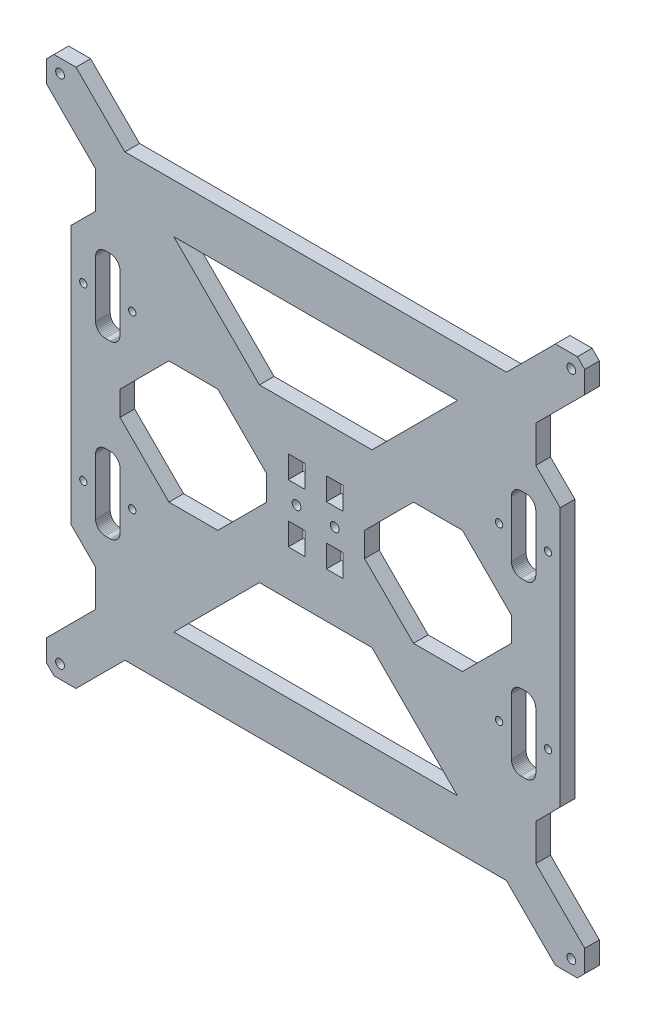
SolidWorks part; units mm, degrees
ref_plane "Plano frontal" through (0, 0, 0) normal (0, 0, 1) x (1, 0, 0)
ref_plane "Plano superior" through (0, 0, 0) normal (0, 1, 0) x (1, 0, 0)
ref_plane "Plano direito" through (0, 0, 0) normal (1, 0, 0) x (0, 0, -1)
sketch "Model" plane through (0, 0, 0) normal (0, 0, 1) x (1, 0, 0)
  line L0 (50.4714, 105.5211) -> (50.0021, 105.2896)
  line L1 (49.567, 104.999) -> (49.1737, 104.654)
  line L2 (50.0021, 105.2896) -> (49.567, 104.999)
  line L3 (40.0021, 14.8256) -> (60.0021, 34.8256)
  line L4 (38.0021, 71.8256) -> (48.0021, 61.8256)
  line L5 (48.0021, 187.8255) -> (38.0021, 177.8255)
  line L6 (28.0021, 26.8256) -> (28.0021, 17.8256)
  line L7 (56.8305, 75.9971) -> (57.1755, 76.3905)
  line L8 (55.5328, 105.5211) -> (55.0374, 105.6892)
  line L9 (55.0374, 105.6892) -> (54.5242, 105.7913)
  line L10 (54.5242, 105.7913) -> (54.0021, 105.8255)
  line L11 (28.0021, 17.8256) -> (31.0021, 14.8256)
  line L12 (57.9679, 78.3034) -> (58.0021, 78.8256)
  line L13 (54.5242, 74.8598) -> (55.0374, 74.9619)
  line L14 (50.4714, 75.13) -> (50.9668, 74.9619)
  line L15 (50.0021, 75.3615) -> (50.4714, 75.13)
  line L16 (56.0021, 105.2896) -> (55.5328, 105.5211)
  line L17 (48.3066, 103.3563) -> (48.1384, 102.8608)
  line L18 (48.1384, 102.8608) -> (48.0363, 102.3476)
  line L19 (48.0363, 102.3476) -> (48.0021, 101.8255)
  line L20 (52.0021, 105.8255) -> (54.0021, 105.8255)
  line L21 (40.0021, 234.8255) -> (60.0021, 214.8255)
  line L22 (49.567, 75.6521) -> (50.0021, 75.3615)
  line L23 (49.1737, 75.9971) -> (49.567, 75.6521)
  line L24 (54.0021, 74.8256) -> (52.0021, 74.8256)
  line L25 (52.0021, 105.8255) -> (51.48, 105.7913)
  line L26 (51.48, 105.7913) -> (50.9668, 105.6892)
  line L27 (48.0021, 78.8256) -> (48.0021, 101.8255)
  line L28 (48.0021, 78.8256) -> (48.0363, 78.3034)
  line L29 (48.0363, 78.3034) -> (48.1384, 77.7903)
  line L30 (28.0021, 222.8255) -> (48.0021, 202.8255)
  line L31 (57.8658, 102.8608) -> (57.6976, 103.3563)
  line L32 (57.9679, 102.3476) -> (57.8658, 102.8608)
  line L33 (58.0021, 101.8255) -> (57.9679, 102.3476)
  line L34 (31.0021, 234.8255) -> (28.0021, 231.8255)
  line L35 (38.0021, 177.8255) -> (38.0021, 71.8256)
  line L36 (57.6976, 103.3563) -> (57.4662, 103.8255)
  line L37 (57.4662, 103.8255) -> (57.1755, 104.2606)
  line L38 (48.0021, 46.8256) -> (48.0021, 61.8256)
  line L39 (48.3066, 77.2948) -> (48.538, 76.8256)
  line L40 (48.538, 76.8256) -> (48.8287, 76.3905)
  line L41 (57.1755, 104.2606) -> (56.8305, 104.654)
  line L42 (48.8287, 76.3905) -> (49.1737, 75.9971)
  line L43 (58.0021, 101.8255) -> (58.0021, 78.8256)
  line L44 (48.538, 103.8255) -> (48.3066, 103.3563)
  line L45 (55.5328, 75.13) -> (56.0021, 75.3615)
  line L46 (56.0021, 75.3615) -> (56.4371, 75.6521)
  line L47 (56.4371, 75.6521) -> (56.8305, 75.9971)
  line L48 (55.0374, 74.9619) -> (55.5328, 75.13)
  line L49 (57.6976, 77.2948) -> (57.8658, 77.7903)
  line L50 (57.8658, 77.7903) -> (57.9679, 78.3034)
  line L51 (56.4371, 104.999) -> (56.0021, 105.2896)
  line L52 (56.8305, 104.654) -> (56.4371, 104.999)
  line L53 (28.0021, 26.8256) -> (48.0021, 46.8256)
  line L54 (48.0021, 202.8255) -> (48.0021, 187.8255)
  line L55 (50.9668, 105.6892) -> (50.4714, 105.5211)
  line L56 (54.0021, 74.8256) -> (54.5242, 74.8598)
  line L57 (50.9668, 74.9619) -> (51.48, 74.8598)
  line L58 (48.8287, 104.2606) -> (48.538, 103.8255)
  line L59 (49.1737, 104.654) -> (48.8287, 104.2606)
  line L60 (57.1755, 76.3905) -> (57.4662, 76.8256)
  line L61 (57.4662, 76.8256) -> (57.6976, 77.2948)
  line L62 (48.1384, 77.7903) -> (48.3066, 77.2948)
  line L63 (51.48, 74.8598) -> (52.0021, 74.8256)
  line L64 (60.0021, 214.8255) -> (216.002, 214.8255)
  line L65 (60.0021, 34.8256) -> (216.002, 34.8256)
  line L66 (57.8658, 172.8678) -> (57.6976, 173.3633)
  line L67 (57.6976, 173.3633) -> (57.4662, 173.8326)
  line L68 (57.1755, 174.2676) -> (56.8305, 174.661)
  line L69 (57.9679, 172.3547) -> (57.8658, 172.8678)
  line L70 (58.0021, 171.8326) -> (57.9679, 172.3547)
  line L71 (58.0021, 171.8326) -> (58.0021, 148.8326)
  line L72 (57.9679, 148.3105) -> (58.0021, 148.8326)
  line L73 (57.8658, 147.7973) -> (57.9679, 148.3105)
  line L74 (57.6976, 147.3018) -> (57.8658, 147.7973)
  line L75 (57.4662, 146.8326) -> (57.6976, 147.3018)
  line L76 (57.1755, 146.3975) -> (57.4662, 146.8326)
  line L77 (56.8305, 146.0041) -> (57.1755, 146.3975)
  line L78 (56.4371, 145.6592) -> (56.8305, 146.0041)
  line L79 (56.0021, 145.3685) -> (56.4371, 145.6592)
  line L80 (55.5328, 145.1371) -> (56.0021, 145.3685)
  line L81 (55.0374, 144.9689) -> (55.5328, 145.1371)
  line L82 (54.5242, 144.8668) -> (55.0374, 144.9689)
  line L83 (54.0021, 144.8326) -> (54.5242, 144.8668)
  line L84 (54.0021, 144.8326) -> (52.0021, 144.8326)
  line L85 (51.48, 144.8668) -> (52.0021, 144.8326)
  line L86 (50.9668, 144.9689) -> (51.48, 144.8668)
  line L87 (50.4714, 145.1371) -> (50.9668, 144.9689)
  line L88 (50.0021, 145.3685) -> (50.4714, 145.1371)
  line L89 (49.567, 145.6592) -> (50.0021, 145.3685)
  line L90 (49.1737, 146.0041) -> (49.567, 145.6592)
  line L91 (48.8287, 146.3975) -> (49.1737, 146.0041)
  line L92 (48.538, 146.8326) -> (48.8287, 146.3975)
  line L93 (48.3066, 147.3018) -> (48.538, 146.8326)
  line L94 (48.1384, 147.7973) -> (48.3066, 147.3018)
  line L95 (48.0363, 148.3105) -> (48.1384, 147.7973)
  line L96 (48.0021, 148.8326) -> (48.0363, 148.3105)
  line L97 (48.0021, 148.8326) -> (48.0021, 171.8326)
  line L98 (48.0363, 172.3547) -> (48.0021, 171.8326)
  line L99 (48.1384, 172.8678) -> (48.0363, 172.3547)
  line L100 (48.3066, 173.3633) -> (48.1384, 172.8678)
  line L101 (48.538, 173.8326) -> (48.3066, 173.3633)
  line L102 (48.8287, 174.2676) -> (48.538, 173.8326)
  line L103 (49.1737, 174.661) -> (48.8287, 174.2676)
  line L104 (49.567, 175.006) -> (49.1737, 174.661)
  line L105 (50.0021, 175.2967) -> (49.567, 175.006)
  line L106 (50.4714, 175.5281) -> (50.0021, 175.2967)
  line L107 (50.9668, 175.6963) -> (50.4714, 175.5281)
  line L108 (51.48, 175.7983) -> (50.9668, 175.6963)
  line L109 (52.0021, 175.8326) -> (51.48, 175.7983)
  line L110 (52.0021, 175.8326) -> (54.0021, 175.8326)
  line L111 (54.5242, 175.7983) -> (54.0021, 175.8326)
  line L112 (55.0374, 175.6963) -> (54.5242, 175.7983)
  line L113 (55.5328, 175.5281) -> (55.0374, 175.6963)
  line L114 (56.0021, 175.2967) -> (55.5328, 175.5281)
  line L115 (56.4371, 175.006) -> (56.0021, 175.2967)
  line L116 (56.8305, 174.661) -> (56.4371, 175.006)
  line L117 (57.4662, 173.8326) -> (57.1755, 174.2676)
  line L118 (80.0021, 194.8255) -> (115.0021, 159.8255)
  line L119 (118.0021, 129.8255) -> (118.0021, 119.8255)
  line L120 (118.0021, 119.8255) -> (98.0021, 99.8255)
  line L121 (98.0021, 99.8255) -> (78.0021, 99.8255)
  line L122 (78.0021, 99.8255) -> (58.0021, 119.8255)
  line L123 (58.0021, 119.8255) -> (58.0021, 129.8255)
  line L124 (58.0021, 129.8255) -> (78.0021, 149.8255)
  line L125 (78.0021, 149.8255) -> (98.0021, 149.8255)
  line L126 (98.0021, 149.8255) -> (118.0021, 129.8255)
  line L127 (115.0021, 89.8255) -> (80.0021, 54.8256)
  line L128 (126.8002, 117.5591) -> (126.8002, 108.3591)
  line L129 (126.8002, 141.3591) -> (126.8002, 132.1591)
  line L130 (133.6002, 108.3591) -> (133.6002, 117.5591)
  line L131 (133.6002, 117.5591) -> (126.8002, 117.5591)
  line L132 (133.6002, 141.3591) -> (126.8002, 141.3591)
  line L133 (126.8002, 132.1591) -> (133.6002, 132.1591)
  line L134 (133.6002, 132.1591) -> (133.6002, 141.3591)
  line L135 (126.8002, 108.3591) -> (133.6002, 108.3591)
  line L136 (28.0021, 231.8255) -> (28.0021, 222.8255)
  line L137 (40.0021, 234.8255) -> (31.0021, 234.8255)
  line L138 (31.0021, 14.8256) -> (40.0021, 14.8256)
  line L139 (98.0021, 149.8255) -> (98.0724, 149.8255)
  line L140 (225.5328, 105.5211) -> (226.002, 105.2896)
  line L141 (226.4371, 104.999) -> (226.8305, 104.654)
  line L142 (226.002, 105.2896) -> (226.4371, 104.999)
  line L143 (236.002, 14.8256) -> (216.002, 34.8256)
  line L144 (238.002, 71.8256) -> (228.002, 61.8256)
  line L145 (228.002, 187.8255) -> (238.002, 177.8255)
  line L146 (248.002, 26.8256) -> (248.002, 17.8256)
  line L147 (219.1736, 75.9971) -> (218.8286, 76.3905)
  line L148 (220.4713, 105.5211) -> (220.9668, 105.6892)
  line L149 (220.9668, 105.6892) -> (221.4799, 105.7913)
  line L150 (221.4799, 105.7913) -> (222.002, 105.8255)
  line L151 (248.002, 17.8256) -> (245.002, 14.8256)
  line L152 (218.0363, 78.3034) -> (218.002, 78.8256)
  line L153 (221.4799, 74.8598) -> (220.9668, 74.9619)
  line L154 (225.5328, 75.13) -> (225.0373, 74.9619)
  line L155 (226.002, 75.3615) -> (225.5328, 75.13)
  line L156 (220.002, 105.2896) -> (220.4713, 105.5211)
  line L157 (227.6975, 103.3563) -> (227.8657, 102.8608)
  line L158 (227.8657, 102.8608) -> (227.9678, 102.3476)
  line L159 (227.9678, 102.3476) -> (228.002, 101.8255)
  line L160 (224.002, 105.8255) -> (222.002, 105.8255)
  line L161 (236.002, 234.8255) -> (216.002, 214.8255)
  line L162 (226.4371, 75.6521) -> (226.002, 75.3615)
  line L163 (226.8305, 75.9971) -> (226.4371, 75.6521)
  line L164 (222.002, 74.8256) -> (224.002, 74.8256)
  line L165 (224.002, 105.8255) -> (224.5241, 105.7913)
  line L166 (224.5241, 105.7913) -> (225.0373, 105.6892)
  line L167 (228.002, 78.8256) -> (228.002, 101.8255)
  line L168 (228.002, 78.8256) -> (227.9678, 78.3034)
  line L169 (227.9678, 78.3034) -> (227.8657, 77.7903)
  line L170 (248.002, 222.8255) -> (228.002, 202.8255)
  line L171 (218.1383, 102.8608) -> (218.3065, 103.3563)
  line L172 (218.0363, 102.3476) -> (218.1383, 102.8608)
  line L173 (218.002, 101.8255) -> (218.0363, 102.3476)
  line L174 (245.002, 234.8255) -> (248.002, 231.8255)
  line L175 (238.002, 177.8255) -> (238.002, 71.8256)
  line L176 (218.3065, 103.3563) -> (218.5379, 103.8255)
  line L177 (218.5379, 103.8255) -> (218.8286, 104.2606)
  line L178 (228.002, 46.8256) -> (228.002, 61.8256)
  line L179 (227.6975, 77.2948) -> (227.4661, 76.8256)
  line L180 (227.4661, 76.8256) -> (227.1754, 76.3905)
  line L181 (218.8286, 104.2606) -> (219.1736, 104.654)
  line L182 (227.1754, 76.3905) -> (226.8305, 75.9971)
  line L183 (218.002, 101.8255) -> (218.002, 78.8256)
  line L184 (227.4661, 103.8255) -> (227.6975, 103.3563)
  line L185 (220.4713, 75.13) -> (220.002, 75.3615)
  line L186 (220.002, 75.3615) -> (219.567, 75.6521)
  line L187 (219.567, 75.6521) -> (219.1736, 75.9971)
  line L188 (220.9668, 74.9619) -> (220.4713, 75.13)
  line L189 (218.3065, 77.2948) -> (218.1383, 77.7903)
  line L190 (218.1383, 77.7903) -> (218.0363, 78.3034)
  line L191 (219.567, 104.999) -> (220.002, 105.2896)
  line L192 (219.1736, 104.654) -> (219.567, 104.999)
  line L193 (248.002, 26.8256) -> (228.002, 46.8256)
  line L194 (228.002, 202.8255) -> (228.002, 187.8255)
  line L195 (225.0373, 105.6892) -> (225.5328, 105.5211)
  line L196 (222.002, 74.8256) -> (221.4799, 74.8598)
  line L197 (225.0373, 74.9619) -> (224.5241, 74.8598)
  line L198 (227.1754, 104.2606) -> (227.4661, 103.8255)
  line L199 (226.8305, 104.654) -> (227.1754, 104.2606)
  line L200 (218.8286, 76.3905) -> (218.5379, 76.8256)
  line L201 (218.5379, 76.8256) -> (218.3065, 77.2948)
  line L202 (227.8657, 77.7903) -> (227.6975, 77.2948)
  line L203 (224.5241, 74.8598) -> (224.002, 74.8256)
  line L204 (218.1383, 172.8678) -> (218.3065, 173.3633)
  line L205 (218.3065, 173.3633) -> (218.5379, 173.8326)
  line L206 (218.8286, 174.2676) -> (219.1736, 174.661)
  line L207 (218.0363, 172.3547) -> (218.1383, 172.8678)
  line L208 (218.002, 171.8326) -> (218.0363, 172.3547)
  line L209 (218.002, 171.8326) -> (218.002, 148.8326)
  line L210 (218.0363, 148.3105) -> (218.002, 148.8326)
  line L211 (218.1383, 147.7973) -> (218.0363, 148.3105)
  line L212 (218.3065, 147.3018) -> (218.1383, 147.7973)
  line L213 (218.5379, 146.8326) -> (218.3065, 147.3018)
  line L214 (218.8286, 146.3975) -> (218.5379, 146.8326)
  line L215 (219.1736, 146.0041) -> (218.8286, 146.3975)
  line L216 (219.567, 145.6592) -> (219.1736, 146.0041)
  line L217 (220.002, 145.3685) -> (219.567, 145.6592)
  line L218 (220.4713, 145.1371) -> (220.002, 145.3685)
  line L219 (220.9668, 144.9689) -> (220.4713, 145.1371)
  line L220 (221.4799, 144.8668) -> (220.9668, 144.9689)
  line L221 (222.002, 144.8326) -> (221.4799, 144.8668)
  line L222 (222.002, 144.8326) -> (224.002, 144.8326)
  line L223 (224.5241, 144.8668) -> (224.002, 144.8326)
  line L224 (225.0373, 144.9689) -> (224.5241, 144.8668)
  line L225 (225.5328, 145.1371) -> (225.0373, 144.9689)
  line L226 (226.002, 145.3685) -> (225.5328, 145.1371)
  line L227 (226.4371, 145.6592) -> (226.002, 145.3685)
  line L228 (226.8305, 146.0041) -> (226.4371, 145.6592)
  line L229 (227.1754, 146.3975) -> (226.8305, 146.0041)
  line L230 (227.4661, 146.8326) -> (227.1754, 146.3975)
  line L231 (227.6975, 147.3018) -> (227.4661, 146.8326)
  line L232 (227.8657, 147.7973) -> (227.6975, 147.3018)
  line L233 (227.9678, 148.3105) -> (227.8657, 147.7973)
  line L234 (228.002, 148.8326) -> (227.9678, 148.3105)
  line L235 (228.002, 148.8326) -> (228.002, 171.8326)
  line L236 (227.9678, 172.3547) -> (228.002, 171.8326)
  line L237 (227.8657, 172.8678) -> (227.9678, 172.3547)
  line L238 (227.6975, 173.3633) -> (227.8657, 172.8678)
  line L239 (227.4661, 173.8326) -> (227.6975, 173.3633)
  line L240 (227.1754, 174.2676) -> (227.4661, 173.8326)
  line L241 (226.8305, 174.661) -> (227.1754, 174.2676)
  line L242 (226.4371, 175.006) -> (226.8305, 174.661)
  line L243 (226.002, 175.2967) -> (226.4371, 175.006)
  line L244 (225.5328, 175.5281) -> (226.002, 175.2967)
  line L245 (225.0373, 175.6963) -> (225.5328, 175.5281)
  line L246 (224.5241, 175.7983) -> (225.0373, 175.6963)
  line L247 (224.002, 175.8326) -> (224.5241, 175.7983)
  line L248 (224.002, 175.8326) -> (222.002, 175.8326)
  line L249 (221.4799, 175.7983) -> (222.002, 175.8326)
  line L250 (220.9668, 175.6963) -> (221.4799, 175.7983)
  line L251 (220.4713, 175.5281) -> (220.9668, 175.6963)
  line L252 (220.002, 175.2967) -> (220.4713, 175.5281)
  line L253 (219.567, 175.006) -> (220.002, 175.2967)
  line L254 (219.1736, 174.661) -> (219.567, 175.006)
  line L255 (218.5379, 173.8326) -> (218.8286, 174.2676)
  line L256 (196.002, 194.8255) -> (161.002, 159.8255)
  line L257 (158.002, 129.8255) -> (158.002, 119.8255)
  line L258 (158.002, 119.8255) -> (178.002, 99.8255)
  line L259 (178.002, 99.8255) -> (198.002, 99.8255)
  line L260 (198.002, 99.8255) -> (218.002, 119.8255)
  line L261 (218.002, 119.8255) -> (218.002, 129.8255)
  line L262 (218.002, 129.8255) -> (198.002, 149.8255)
  line L263 (198.002, 149.8255) -> (178.002, 149.8255)
  line L264 (178.002, 149.8255) -> (158.002, 129.8255)
  line L265 (161.002, 89.8255) -> (196.002, 54.8256)
  line L266 (149.2039, 117.5591) -> (149.2039, 108.3591)
  line L267 (149.2039, 141.3591) -> (149.2039, 132.1591)
  line L268 (142.4039, 108.3591) -> (142.4039, 117.5591)
  line L269 (142.4039, 117.5591) -> (149.2039, 117.5591)
  line L270 (142.4039, 141.3591) -> (149.2039, 141.3591)
  line L271 (149.2039, 132.1591) -> (142.4039, 132.1591)
  line L272 (142.4039, 132.1591) -> (142.4039, 141.3591)
  line L273 (149.2039, 108.3591) -> (142.4039, 108.3591)
  line L274 (248.002, 231.8255) -> (248.002, 222.8255)
  line L275 (236.002, 234.8255) -> (245.002, 234.8255)
  line L276 (245.002, 14.8256) -> (236.002, 14.8256)
  line L277 (178.002, 149.8255) -> (177.9317, 149.8255)
  line L278 (115.0021, 89.8255) -> (161.002, 89.8255)
  line L279 (80.0021, 54.8256) -> (196.002, 54.8256)
  line L280 (80.0021, 194.8255) -> (196.002, 194.8255)
  line L281 (115.0021, 159.8255) -> (161.002, 159.8255)
  circle A0 centre (33.4917, 20.336) radius 1.8
  circle A1 centre (63.0021, 89.8255) radius 1.5
  circle A2 centre (43.0021, 89.8511) radius 1.5
  circle A3 centre (130.1985, 124.8594) radius 1.8
  circle A4 centre (33.4917, 229.3359) radius 1.8
  circle A5 centre (63.0021, 159.8255) radius 1.5
  circle A6 centre (43.0021, 159.8255) radius 1.5
  circle A7 centre (242.5124, 20.336) radius 1.8
  circle A8 centre (213.002, 89.8255) radius 1.5
  circle A9 centre (233.002, 89.8511) radius 1.5
  circle A10 centre (145.8056, 124.8594) radius 1.8
  circle A11 centre (242.5124, 229.3359) radius 1.8
  circle A12 centre (213.002, 159.8255) radius 1.5
  circle A13 centre (233.002, 159.8255) radius 1.5
extrude "Ressalto-extrusão1" add sketch "Model" along normal blind 6 contours L276 L151 L146 L193 L178 L144 L175 L145 L194 L170 L274 L174 L275 L161 L64 L21 L137 L34 L136 L30 L54 L5 L35 L4 L38 L53 L6 L11 L138 L3 L65 L143 A13 A12 A11 A10 A9 A8 A7 A6 A5 region at (138.0021, 124.8013, 0)
ref_plane "Plano1" through (53.0021, 0, 0) normal (1, 0, 0) x (0, 0, -1)
ref_plane "Plano2" through (223.002, 0, 0) normal (1, 0, 0) x (0, 0, -1)
